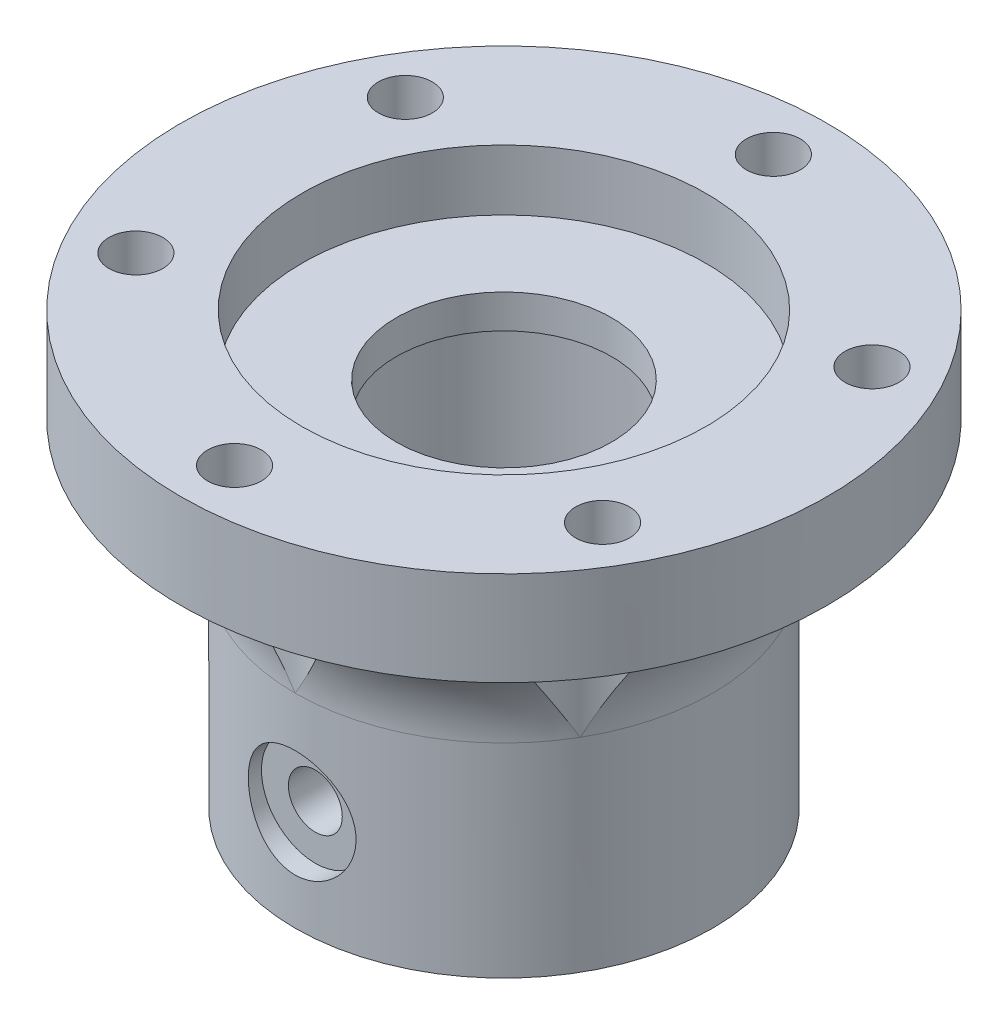
SolidWorks part; units mm, degrees
ref_plane "Спереди" through (0, 0, 0) normal (0, 0, 1) x (1, 0, 0)
ref_plane "Сверху" through (0, 0, 0) normal (0, 1, 0) x (1, 0, 0)
ref_plane "Справа" through (0, 0, 0) normal (1, 0, 0) x (0, 0, -1)
sketch "Эскиз1" plane through (0, 0, 0) normal (0, 1, 0) x (1, 0, 0)
  circle A0 centre (0, 0) radius 10.5
  circle A1 centre (0, 0) radius 15.5
extrude "Вытянуть1" add sketch "Эскиз1" along normal blind 25
sketch "Эскиз3" plane through (0, 25, 0) normal (0, 1, 0) x (1, 0, 0)
  circle A0 centre (0, 0) radius 24
extrude "Вытянуть2" add sketch "Эскиз3" along normal blind 7
fillet "Скругление1" radius 10 1 edges at (0, 25, 15.5)
sketch "Эскиз5" plane through (0, 32, 0) normal (0, 1, 0) x (1, 0, 0)
  circle A0 centre (0, 0) radius 15
extrude "Вытянуть3" cut sketch "Эскиз5" against normal blind 4.5
sketch "Эскиз6" plane through (0, 27.5, 0) normal (0, 1, 0) x (1, 0, 0)
  circle A0 centre (0, 0) radius 8
extrude "Вытянуть4" cut sketch "Эскиз6" against normal through all
sketch "Эскиз7" plane through (0, 32, 0) normal (0, 1, 0) x (1, 0, 0)
  circle A0 centre (0, -20) radius 2
  circle A1 centre (-17.3205, -10) radius 2
  circle A2 centre (-17.3205, 10) radius 2
  circle A3 centre (0, 20) radius 2
  circle A4 centre (17.3205, 10) radius 2
  circle A5 centre (17.3205, -10) radius 2
extrude "Вытянуть5" cut sketch "Эскиз7" against normal through all
sketch "Эскиз8" plane through (0, 32, 0) normal (0, 1, 0) x (1, 0, 0)
  circle A0 centre (0, -20) radius 4.5
  circle A1 centre (-17.3205, -10) radius 4.5
  circle A2 centre (-17.3205, 10) radius 4.5
  circle A3 centre (0, 20) radius 4.5
  circle A4 centre (17.3205, 10) radius 4.5
  circle A5 centre (17.3205, -10) radius 4.5
extrude "Вытянуть6" cut sketch "Эскиз8" against normal blind 10 from offset 7
sketch "Эскиз9" plane through (0, 0, 0) normal (0, 0, 1) x (1, 0, 0)
  circle A0 centre (0, 7.4236) radius 2
extrude "Вытянуть7" cut sketch "Эскиз9" against normal mid plane 40
sketch "Эскиз11" plane through (0, 0, 0) normal (0, 0, 1) x (1, 0, 0)
  circle A0 centre (0, 7.4236) radius 4
extrude "Вытянуть8" cut sketch "Эскиз11" against normal blind 40 from offset 14
sketch "Эскиз12" plane through (0, 0, 0) normal (0, 0, 1) x (1, 0, 0)
  circle A0 centre (0, 7.4236) radius 4
extrude "Вытянуть9" cut sketch "Эскиз12" along normal blind 40 from offset 14
